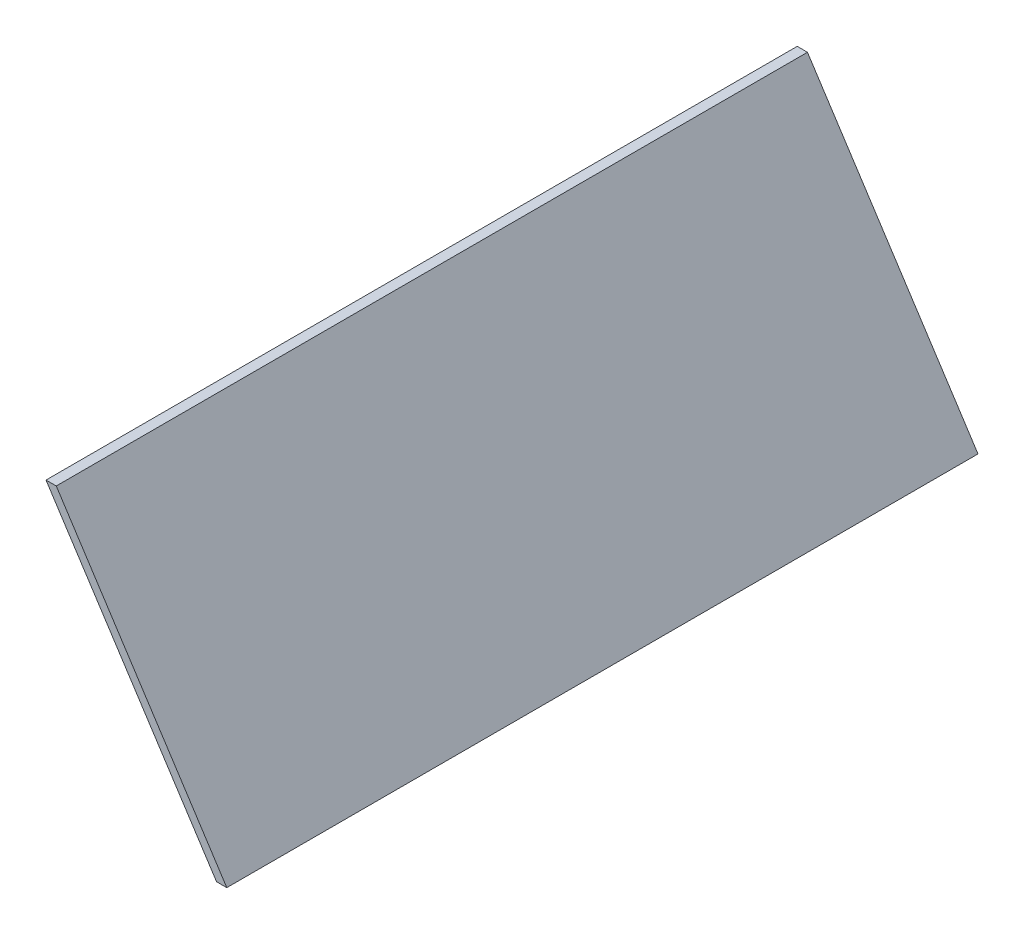
SolidWorks part; units mm, degrees
material "5052-H34"
ref_plane "Front Plane" through (0, 0, 0) normal (0, 0, 1) x (1, 0, 0)
ref_plane "Top Plane" through (0, 0, 0) normal (0, 1, 0) x (1, 0, 0)
ref_plane "Right Plane" through (0, 0, 0) normal (1, 0, 0) x (0, 0, -1)
sketch "Sketch1" plane through (0, 0, 0) normal (0, 0, 1) x (1, 0, 0)
  line L7 (-148.6264, -87.4926) -> (-144.8407, -87.4926)
  line L10 (-144.8407, -87.4926) -> (-125.3132, -87.4926) construction
  line L11 (-199.8594, 9.5074) -> (-217.2492, 9.5074) construction
  line L15 (-211.619, 9.5074) -> (-207.8332, 9.5074)
  line L16 (-207.8332, 9.5074) -> (-144.8407, -87.4926)
  line L17 (-211.619, 9.5074) -> (-148.6264, -87.4926)
  point P0 (-199.8594, 9.5074)
  dimension "D1" = 123
  dimension "D2" = 3.175
  dimension "D3" = 97
extrude "Boss-Extrude1" add sketch "Sketch1" along normal blind 277.48 contours L15 L16 L7 L17
